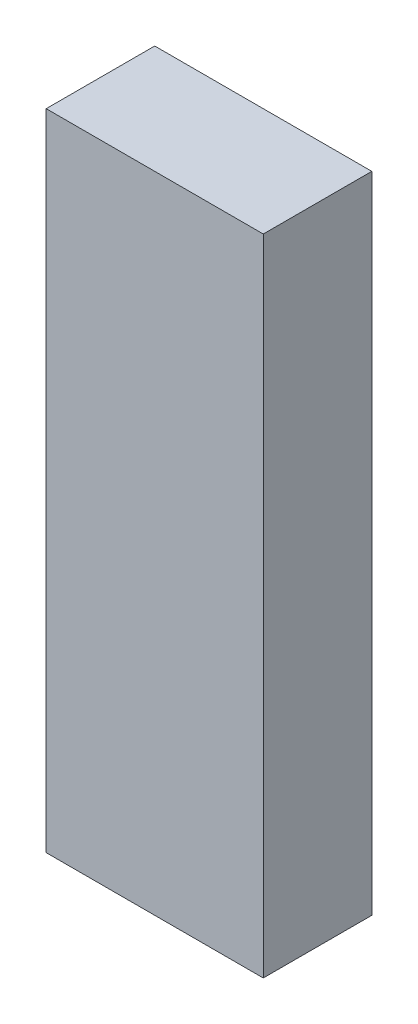
SolidWorks part; units mm, degrees
ref_plane "Front Plane" through (0, 0, 0) normal (0, 0, 1) x (1, 0, 0)
ref_plane "Top Plane" through (0, 0, 0) normal (0, 1, 0) x (1, 0, 0)
ref_plane "Right Plane" through (0, 0, 0) normal (1, 0, 0) x (0, 0, -1)
sketch "Sketch1" plane through (0, 0, 0) normal (0, 1, 0) x (1, 0, 0)
  line L0 (-200, -100) -> (200, -100)
  line L4 (200, -100) -> (200, 100)
  line L5 (-200, -100) -> (200, 100) construction
  line L6 (-200, 100) -> (200, -100) construction
  line L9 (200, 100) -> (-200, 100)
  line L10 (-200, -100) -> (-200, 100)
  point P0 (0, 0)
  dimension "D1" = 400
  dimension "D3" = 200
extrude "Boss-Extrude1" add sketch "Sketch1" along normal blind 1187.25
